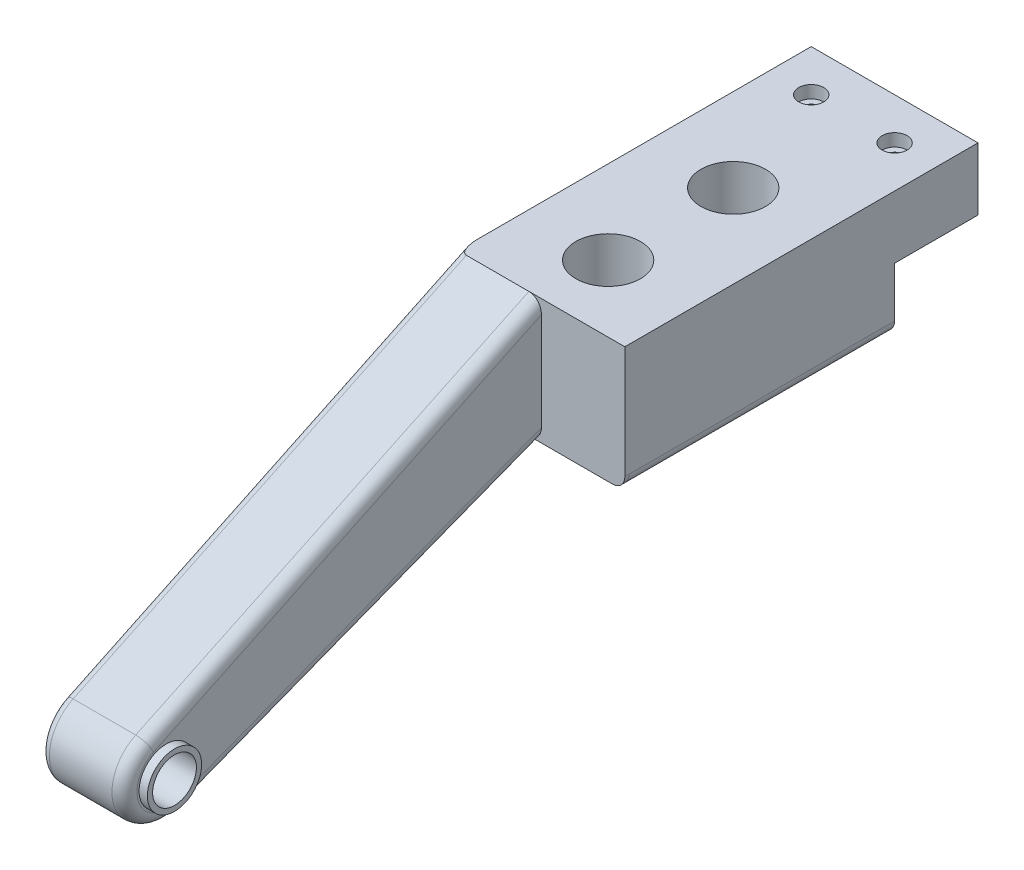
SolidWorks part; units mm, degrees
ref_plane "Front Plane" through (0, 0, 0) normal (0, 0, 1) x (1, 0, 0)
ref_plane "Top Plane" through (0, 0, 0) normal (0, 1, 0) x (1, 0, 0)
ref_plane "Right Plane" through (0, 0, 0) normal (1, 0, 0) x (0, 0, -1)
sketch "Sketch1" plane through (0, 0, 0) normal (0, 1, 0) x (1, 0, 0)
  line L1 (-20, 75) -> (20, 75)
  line L3 (-20, -75) -> (20, -75)
  line L4 (20, -75) -> (20, 75)
  line L5 (-20, -75) -> (-20, 75)
  circle A0 centre (0, -61.1649) radius 7.5
  circle A1 centre (0, -31.1649) radius 7.5
extrude "Boss-Extrude1" add sketch "Sketch1" against normal blind 30 contours L5 L1 L4 L3
sketch "Sketch3" plane through (0, 0, 0) normal (0, 1, 0) x (1, 0, 0)
  circle A0 centre (0, -60) radius 7.5
  circle A1 centre (0, -30) radius 7.5
extrude "Cut-Extrude1" cut sketch "Sketch3" against normal blind 30 contours A0 | A1
sketch "Sketch4" plane through (-20, 0, 0) normal (-1, 0, 0) x (0, 0, 1)
  line L1 (-75, -30) -> (-75, 0) construction
  line L2 (-75, -8) -> (0, -30)
  line L3 (75, -30) -> (-75, -30) construction
  line L4 (0, -30) -> (-75, -30)
  line L5 (-75, -30) -> (-75, -8)
extrude "Cut-Extrude2" cut sketch "Sketch4" against normal blind 49
sketch "Sketch6" plane through (0, 0, -75) normal (0, 0, -1) x (-1, 0, 0)
  line L1 (-20, 0) -> (20, 0)
  line L2 (-20, 0) -> (-20, -30)
  line L3 (-20, -30) -> (20, -30)
  line L4 (20, 0) -> (20, -30)
extrude "Boss-Extrude2" add sketch "Sketch6" along normal blind 50 and the other way blind 87
sketch "Sketch7" plane through (-20, 0, 0) normal (-1, 0, 0) x (0, 0, 1)
  line L1 (-125, -30) -> (-125, 0) construction
  line L2 (-125, -10) -> (-25, -30)
  line L3 (75, -30) -> (-125, -30) construction
  line L4 (-25, -30) -> (-125, -30)
  line L5 (-125, -30) -> (-125, -10)
extrude "Cut-Extrude3" cut sketch "Sketch7" against normal blind 50
sketch "Sketch8" plane through (0, 0, 75) normal (0, 0, 1) x (1, 0, 0)
  line L10 (20, -30) -> (6, -30)
  line L11 (-20, -30) -> (20, -30) construction
  line L12 (6, -30) -> (6, 0)
  line L13 (-20, 0) -> (20, 0) construction
  line L14 (6, 0) -> (20, 0)
  line L15 (20, 0) -> (20, -30)
  line L16 (-20, -30) -> (-6, -30)
  line L17 (-6, -30) -> (-6, 0)
  line L18 (-6, 0) -> (-20, 0)
  line L19 (-20, -30) -> (-20, 0) construction
  line L20 (-20, 0) -> (-20, -30)
extrude "Boss-Extrude4" add sketch "Sketch8" along normal blind 50
sketch "Sketch11" plane through (0, 0, 0) normal (0, 1, 0) x (1, 0, 0)
  line L0 (6, -75) -> (20, -75)
  line L1 (20, -125) -> (20, 125) construction
  line L2 (20, -75) -> (20, -125)
  line L3 (20, -125) -> (6, -125)
  line L4 (6, -125) -> (6, -75)
  line L5 (-6, -75) -> (-6, -125)
  line L6 (-6, -125) -> (-20, -125)
  line L7 (-20, -125) -> (-20, -75)
  line L8 (-20, -125) -> (-20, 125) construction
  line L9 (-20, -75) -> (-6, -75)
extrude "Cut-Extrude4" cut sketch "Sketch11" against normal blind 15
sketch "Sketch12" plane through (0, 0, 125) normal (0, 0, 1) x (1, 0, 0)
  line L1 (-20, -15) -> (-6, -15)
  line L2 (-20, -15) -> (-20, -30)
  line L3 (-20, -30) -> (-6, -30)
  line L4 (-6, -15) -> (-6, -30)
  line L5 (6, -15) -> (20, -15)
  line L6 (6, -15) -> (6, -30)
  line L7 (6, -30) -> (20, -30)
  line L8 (20, -15) -> (20, -30)
extrude "Boss-Extrude5" add sketch "Sketch12" along normal blind 10
sketch "Sketch13" plane through (-6, 0, 0) normal (1, 0, 0) x (0, 0, -1)
  circle A0 centre (-125, -22.5) radius 5
extrude "Boss-Extrude6" add sketch "Sketch13" along normal up to surface (12 mm away) contours A0 up to face at (6, -22.5, 105)
sketch "Sketch14" plane through (0, -30, 0) normal (0, -1, 0) x (1, 0, 0)
  circle A0 centre (0, 60) radius 7.5
  circle A1 centre (0, 60) radius 6
  circle A2 centre (0, 30) radius 6
  circle A3 centre (0, 30) radius 7.5
extrude "Boss-Extrude7" add sketch "Sketch14" against normal blind 5
sketch "Sketch15" plane through (20, 0, 0) normal (1, 0, 0) x (0, 0, -1)
  line L0 (125, 0) -> (105, 0)
  line L1 (-75, 0) -> (125, 0) construction
  circle A0 centre (52.5, 373.9316) radius 377.5991
extrude "Cut-Extrude5" cut sketch "Sketch15" against normal blind 50 contours A0
fillet "Fillet1" radius 3 2 edges at (20, -30, 55) (-20, -30, 55)
fillet "Fillet2" radius 3 8 edges at (-20, -18.5, -82.5) (-19.1213, -29.1213, -29.3934) (0, -30, -25) (19.1213, -29.1213, -29.3934) (-20, -5, -125) (20, -5, -125) (0, -10, -125) (20, -18.5, -82.5)
sketch "Sketch17" plane through (0, 0, 75) normal (0, 0, 1) x (1, 0, 0)
  line L0 (20, 0) -> (20, -30)
  line L1 (14.0365, -30) -> (20, -30)
  line L2 (6, -30) -> (17, -30) construction
  line L3 (20, 0) -> (-20, 0)
  line L4 (-20, 0) -> (-20, -30)
  line L5 (-20, -30) -> (14.0365, -30)
extrude "Boss-Extrude11" add sketch "Sketch17" along normal up to surface (60 mm away) up to face at (13.9243, -23.5243, 135)
sketch "Sketch23" plane through (0, 0, 135) normal (0, 0, 1) x (1, 0, 0)
  line L0 (-20, -15) -> (0, -15)
  line L1 (-20, 0) -> (-20, -30) construction
  line L3 (0, -30) -> (0, -15)
  line L4 (-20, -30) -> (20, -30) construction
  line L6 (-20, -30) -> (0, -30)
  line L7 (-20, -15) -> (-20, -30)
  line L9 (-20, -30) -> (20, -30)
  line L10 (-20, -30) -> (-20, 0)
  line L11 (-20, 0) -> (20, 0)
  line L12 (20, -30) -> (20, 0)
  line M1 (-20, 0) -> (-20, -30)
  line M2 (-20, -30) -> (20, -30)
  line M3 (20, -30) -> (20, 0)
  line M4 (20, 0) -> (-20, 0)
extrude "Cut-Extrude8" cut sketch "Sketch23" against normal up to surface (60 mm away) contours L3 L0 M2 M3 M4 M1 region at (3.3333, -12.5, 135) up to face at (19.2071, -29.2071, 75)
sketch "Sketch25" plane through (0, 0, 75) normal (0, 0, 1) x (1, 0, 0)
  line L0 (-20, -15) -> (-20, 0)
  line L1 (-20, 0) -> (0, 0)
  line L2 (-20, 0) -> (20, 0) construction
  line L3 (0, 0) -> (0, -15)
  line L4 (0, -15) -> (-20, -15)
extrude "Boss-Extrude13" add sketch "Sketch25" along normal up to surface (60 mm away) up to face at (-10, -22.5, 135)
sketch "Sketch26" plane through (0, 0, 0) normal (1, 0, 0) x (0, 0, -1)
  circle A0 centre (-125, -15) radius 5
extrude "Boss-Extrude14" add sketch "Sketch26" along normal up to surface (20 mm away) up to face at (20, -9.3154, -31.9576)
sketch "Sketch27" plane through (0, 0, 75) normal (0, 0, 1) x (1, 0, 0)
  line L1 (20, 0) -> (-20, 0)
  line L2 (20, 0) -> (20, -60)
  line L3 (20, -60) -> (-20, -60)
  line L4 (-20, 0) -> (-20, -60)
extrude "Boss-Extrude15" add sketch "Sketch27" along normal up to surface (60 mm away) up to face at (-10, -15, 135)
sketch "Sketch28" plane through (0, 0, 75) normal (0, 0, -1) x (-1, 0, 0)
  line L0 (20, -27) -> (20, -60) construction
  line L1 (-20, -60) -> (20, -60)
  line L2 (-20, -60) -> (-20, -30)
  line L3 (-20, -30) -> (20, -30)
  line L4 (20, -60) -> (20, -30)
extrude "Cut-Extrude9" cut sketch "Sketch28" against normal blind 1
sketch "Sketch29" plane through (0, 0, 135) normal (0, 0, 1) x (1, 0, 0)
  line L0 (20, 0) -> (-20, 0) construction
  line L1 (20, -60) -> (0, -60)
  line L2 (20, -60) -> (20, 0)
  line L3 (20, 0) -> (0, 0)
  line L4 (0, -60) -> (0, 0)
extrude "Cut-Extrude10" cut sketch "Sketch29" against normal up to surface (59 mm away) up to face at (0, -45, 76)
fillet "Fillet6" radius 3 1 edges at (-20, -30, 75.5)
fillet "Fillet7" radius 3 1 edges at (20, -30, 75.5)
sketch "Sketch30" plane through (0, 0, 135) normal (0, 0, 1) x (1, 0, 0)
  line L0 (-20, 0) -> (-20, -30)
  line L1 (-20, 0) -> (-20, -60) construction
  line L2 (-20, -15) -> (0, -15)
  line L3 (0, 0) -> (0, -60) construction
  line L4 (0, -15) -> (0, 0)
  line L5 (0, 0) -> (-20, 0)
  line M1 (0, -60) -> (0, 0)
  line M2 (0, 0) -> (-20, 0)
  line M3 (-20, 0) -> (-20, -60)
extrude "Cut-Extrude11" cut sketch "Sketch30" against normal up to surface (59 mm away) contours L2 M3 M1 M2 region at (-10, -7.5, 135) up to face at (11.5243, -17.5243, 76)
sketch "Sketch31" plane through (0, 0, 0) normal (1, 0, 0) x (0, 0, -1)
  line L0 (-129.7694, -41.2162) -> (-129.0122, -40.847)
  line L1 (-76, -15) -> (-76, -30)
  line L2 (-76, -30) -> (-118.7075, -57.7744)
  line L3 (-129.6113, -41.0081) -> (-129.7694, -41.2162)
  line L4 (-89.6197, -15) -> (-129.6113, -41.0081)
  line L5 (-76, -30) -> (-76, -60)
  line L6 (-76, -60) -> (-135, -60)
  line L7 (-135, -60) -> (-135, -15)
  line L8 (-135, -15) -> (-76, -15)
  line L9 (-96, -19.1494) -> (-129.6113, -41.0081) construction
  line L10 (-96, -15) -> (-96, -19.1494) construction
  circle A0 centre (-125.0122, -50.0122) radius 10
  line M9 (-76, -15) -> (-135, -15)
  line M10 (-135, -15) -> (-135, -60)
  line M11 (-135, -60) -> (-76, -60)
  line M12 (-76, -60) -> (-76, -30)
  dimension "D1" = 20
extrude "Cut-Extrude13" cut sketch "Sketch31" against normal blind 28 contours A0 M10 M11 | A0 L2 M11 M12 | A0 L3 L4 M9 M10 region at (0, -24.9817, 119.9741) region at (0, -57.7806, 132.7806) region at (0, -50.0084, 91.4032)
sketch "Sketch32" plane through (0, 0, 0) normal (1, 0, 0) x (0, 0, -1)
  line L0 (-76, -30) -> (-76, 0)
  line L1 (-76, 0) -> (-129.7694, -41.2162)
  line L2 (-129.7694, -41.2162) -> (-76, -30)
extrude "Boss-Extrude16" add sketch "Sketch32" against normal up to surface (20 mm away) up to face at (-20, -28.5466, 55.3206)
sketch "Sketch33" plane through (0, 0, 0) normal (1, 0, 0) x (0, 0, -1)
  circle A0 centre (-125.0122, -50.0122) radius 5
extrude "Boss-Extrude17" add sketch "Sketch33" along normal up to surface (20 mm away) contours A0 up to face at (20, -11.526, -18.3379)
sketch "Sketch34" plane through (0, 0, 0) normal (1, 0, 0) x (0, 0, -1)
  line L3 (-115.822, -61.5953) -> (-76, -30)
  line L4 (-133.1492, -37.6664) -> (-76, 0)
  line L5 (-76, 0) -> (-76, -30)
  circle A0 centre (-166, -50.0122) radius 10
  arc A1 (-133.1492, -37.6664) -> (-115.822, -61.5953) centre (-125.0122, -50.0122) ccw
extrude "Cut-Extrude15" cut sketch "Sketch34" against normal blind 23 and the other way blind 23
ref_plane "Plane2" through (0, 0, 0) normal (-1, 0, 0) x (0, -1, 0)
sketch "Sketch37" plane through (0, 0, 0) normal (-1, 0, 0) x (0, -1, 0)
  line L0 (40.8407, 169.9854) -> (0, 76)
  line L1 (0, 76) -> (30, 76)
  line L2 (30, 76) -> (59.1837, 162.0146)
  arc A0 (59.1837, 162.0146) -> (40.8407, 169.9854) centre (50.0122, 166) ccw
extrude "Boss-Extrude18" add sketch "Sketch37" along normal up to surface (20 mm away) up to face at (-20, -11.526, -18.3379)
sketch "Sketch39" plane through (0, -4.0358, 0) normal (1, 0, 0) x (0, 0, -1)
  circle A0 centre (-166, -50.0122) radius 4.5
extrude "Boss-Extrude19" add sketch "Sketch39" along normal up to surface (12 mm away)
ref_plane "Plane3" through (0, 0, 0) normal (1, 0, 0) x (0, 0, -1)
sketch "Sketch40" plane through (0, 0, 0) normal (1, 0, 0) x (0, 0, -1)
  line L0 (-166, -54.048) -> (-166, -54.0122)
  line L1 (-162.3998, -63.3416) -> (-76, -30)
  line L2 (-76, -30) -> (-76, 0)
  line L3 (-170.3055, -44.9865) -> (-76, 0)
  line L4 (-175.987, -54.5224) -> (-180.0505, -45.7105)
  line L5 (-180.0505, -45.7105) -> (-178.0187, -30)
  line L6 (-178.0187, -30) -> (-76, 0)
  circle A0 centre (-166, -54.0122) radius 10
extrude "Cut-Extrude16" cut sketch "Sketch40" against normal blind 20 contours A0 L3 L6 L5 L4 region at (0, -26.9045, 145.2184)
extrude "Boss-Extrude20" add sketch "Sketch40<3>" against normal blind 20 contours A0 L1 L2 L3 | A0 region at (0, -31.8967, 115.5261) region at (0, -62.1629, 171.2905)
sketch "Sketch40<3>" plane through (0, 0, 0) normal (1, 0, 0) x (0, 0, -1) same geometry as "Sketch40"
fillet "Fillet8" radius 2 3 edges at (-20, -22.4933, 123.1528) (-20, -57.968, 175.1843) (-20, -46.6708, 119.1999)
fillet "Fillet9" radius 3 3 edges at (0, -46.6708, 119.1999) (0, -57.968, 175.1843) (0, -22.4933, 123.1528)
sketch "Sketch42" plane through (20, 0, 0) normal (1, 0, 0) x (0, 0, -1)
  line L0 (105, 0) -> (0, 0)
  line L1 (0, 0) -> (0, -5.8264)
  line L2 (0, -5.8264) -> (105, -5.8264)
  line L3 (105, -5.8264) -> (105, 0)
extrude "Boss-Extrude22" add sketch "Sketch42" against normal up to surface (40 mm away) up to face at (-20, -21.0341, 24.0256)
sketch "Sketch43" plane through (-20, 0, 0) normal (-1, 0, 0) x (0, 0, 1)
  line L0 (71.3548, 0) -> (-122, 0) construction
  line L1 (-24.7029, 0) -> (15.2971, 0)
  line L3 (-24.7029, -27) -> (15.2971, -27)
  line L4 (15.2971, 0) -> (15.2971, -27)
  line L5 (-24.7029, -27) -> (75, -27) construction
  line L6 (-18.7029, -6) -> (9.2971, -6)
  line L7 (9.2971, -6) -> (9.2971, -21)
  line L8 (-18.7029, -21) -> (9.2971, -21)
  line L12 (-18.7029, -21) -> (-93.7029, -6)
  line L13 (-18.7029, -6) -> (-93.7029, -6)
  line L15 (-18.7029, -6) -> (-18.7029, -21) construction
  line L16 (-24.7029, 0) -> (-24.7029, -27) construction
  dimension "D1" = 6
extrude "Cut-Extrude17" cut sketch "Sketch43" against normal blind 59 contours L6 L13 L12 L8 L7 region at (-20, -12.0687, -27.0312)
fillet "Fillet10" radius 2 1 edges at (0, -6, -93.7029)
sketch "Sketch45" plane through (0, 0, 9.2971) normal (0, 0, -1) x (-1, 0, 0)
  line L1 (-20, -21) -> (20, -21)
  line L2 (-20, -21) -> (-20, -6)
  line L3 (-20, -6) -> (20, -6)
  line L4 (20, -21) -> (20, -6)
extrude "Boss-Extrude24" add sketch "Sketch45" along normal blind 28
sketch "Sketch46" plane through (20, 0, 0) normal (1, 0, 0) x (0, 0, -1)
  line L0 (18.7029, -6) -> (18.7029, 0)
  line L1 (-76, 0) -> (122, 0) construction
  line L2 (18.7029, 0) -> (-21.2971, 0)
  line L3 (-21.2971, 0) -> (-21.2971, -30)
  line L4 (-21.2971, -30) -> (18.7029, -30)
  line L5 (18.7029, -30) -> (18.7029, -6)
  line L6 (18.7029, 0) -> (8.7029, 0)
  line L7 (8.7029, 0) -> (8.7029, -15)
  line L8 (8.7029, -15) -> (-11.2971, -15)
  line L9 (-11.2971, -15) -> (-11.2971, -30)
  line M6 (18.7029, -21) -> (18.7029, -6)
  line M10 (122, 0) -> (-76, 0)
  line M13 (-75, -27) -> (24.7029, -27)
sketch "Sketch47" plane through (0, 0, 0) normal (0, 1, 0) x (1, 0, 0)
  line L0 (20, 18.7029) -> (-20, 18.7029)
  line L1 (-20, -71.3548) -> (-20, 122) construction
  line L2 (-20, 18.7029) -> (-20, -1.2971)
  line L3 (-20, -1.2971) -> (-10, -1.2971)
  line L4 (-10, -1.2971) -> (10, -1.2971)
  circle A0 centre (10, -1.2971) radius 1.5
  circle A1 centre (-10, -1.2971) radius 1.5
extrude "Cut-Extrude18" cut sketch "Sketch46" against normal blind 49 contours L8 L9 L5 L0 L7 M13 M6 M10 | L9 L4 L5 M13 region at (20, -17.0294, -6.6441) region at (20, -28.5, -3.7029)
sketch "Sketch48" plane through (0, 0, -18.7029) normal (0, 0, 1) x (1, 0, 0)
  line L1 (23.5648, -32.8586) -> (-26.7549, -32.8586)
  line L2 (23.5648, -32.8586) -> (23.5648, 14.6986)
  line L3 (23.5648, 14.6986) -> (-26.7549, 14.6986)
  line L4 (-26.7549, -32.8586) -> (-26.7549, 14.6986)
extrude "Cut-Extrude19" cut sketch "Sketch48" against normal blind 139
extrude "Cut-Extrude20" cut sketch "Sketch47" against normal blind 139 contours A0 | L4 A1 L3 | L3 A1 L4 region at (-10, 0, 0.6604) region at (10, 0, -0.1605) region at (-10, 0, 1.9337)
sketch "Sketch49" plane through (0, 0, 0) normal (0, 1, 0) x (1, 0, 0)
  circle A0 centre (10, -1.2971) radius 1.5
  circle A1 centre (10, -1.2971) radius 3
  circle A2 centre (-10, -1.2971) radius 1.5
  circle A3 centre (-10, -1.2971) radius 3
extrude "Cut-Extrude21" cut sketch "Sketch49" against normal blind 3
sketch "Sketch51" plane through (0, 0, 0) normal (0, 1, 0) x (1, 0, 0)
  circle A0 centre (0, -60) radius 7.75
  circle A1 centre (0, -30) radius 7.75
extrude "Cut-Extrude23" cut sketch "Sketch51" against normal up to surface (25 mm away) up to face at (0, -25, 54)
sketch "Sketch52" plane through (-20, 0, 0) normal (-1, 0, 0) x (0, 0, 1)
  line L0 (169.4444, -46.7917) -> (163.1198, -61.4757)
  line L1 (166.2821, -54.1337) -> (158.6525, -50.8476)
  circle A0 centre (166, -54.0122) radius 5.25
  circle A1 centre (166, -54.0122) radius 8
  circle A2 centre (158.6525, -50.8476) radius 1.45
extrude "Cut-Extrude24" cut sketch "Sketch52" against normal blind 34 contours L0 A0 | L0 A0 L1 | L1 A0 L0 region at (-20, -54.9596, 168.1997) region at (-20, -51.1245, 164.9974) region at (-20, -55.2676, 163.2129)
extrude "Cut-Extrude25" cut sketch "Sketch52<3>" against normal blind 10 contours L1 A2 A1 | A1 A2 L1 | A1 A2 region at (-20, -50.5522, 159.4749) region at (-20, -50.6137, 158.1096) region at (-20, -51.648, 159.0029)
sketch "Sketch52<3>" plane through (-20, 0, 0) normal (-1, 0, 0) x (0, 0, 1) same geometry as "Sketch52"
sketch "Sketch54" plane through (0, 0, 0) normal (1, 0, 0) x (0, 0, -1)
sketch "Sketch55" plane through (0, 0, 0) normal (1, 0, 0) x (0, 0, -1)
  circle A0 centre (-166, -54.0122) radius 6.5
  circle A1 centre (-166, -54.0122) radius 5.25
extrude "Boss-Extrude25" add sketch "Sketch55" along normal blind 2
